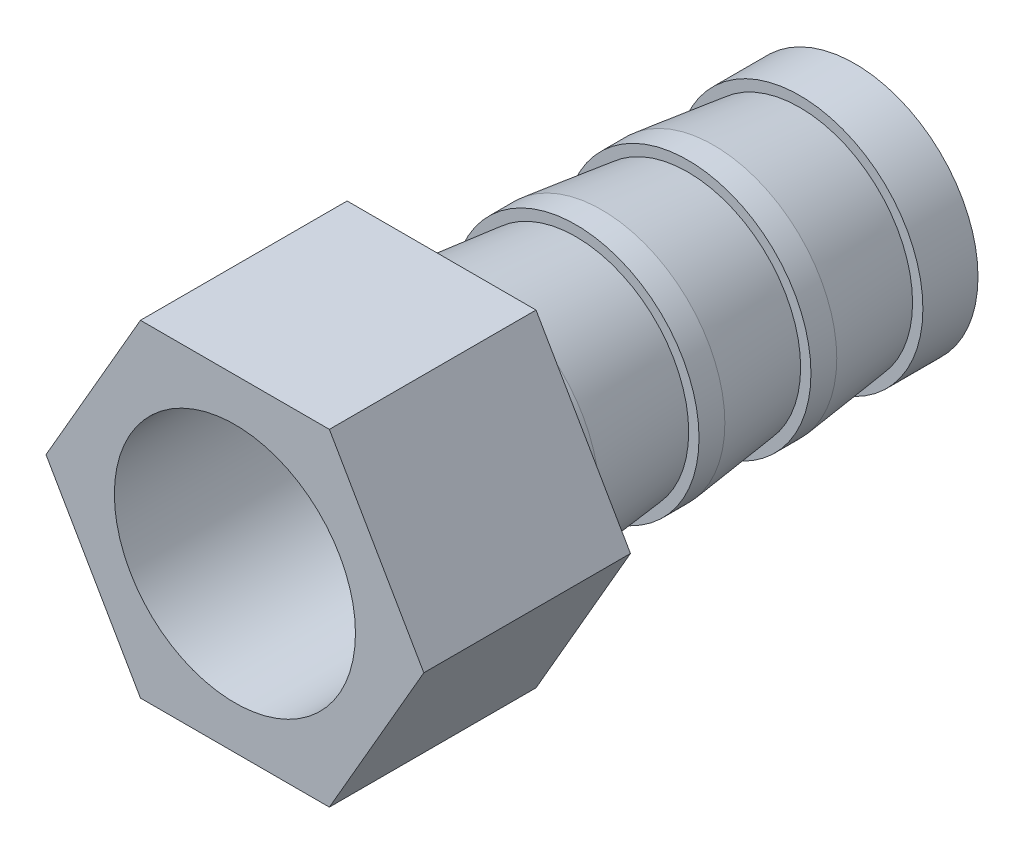
SolidWorks part; units mm, degrees
material "黄铜"
ref_plane "前视基准面" through (0, 0, 0) normal (0, 0, 1) x (1, 0, 0)
ref_plane "上视基准面" through (0, 0, 0) normal (0, 1, 0) x (1, 0, 0)
ref_plane "右视基准面" through (0, 0, 0) normal (1, 0, 0) x (0, 0, -1)
other "质心 (COM)"
sketch "草图1" plane through (0, 0, 0) normal (0, 0, 1) x (1, 0, 0)
  line L1 (5.4848, 9.5) -> (-5.4848, 9.5)
  line L2 (-5.4848, 9.5) -> (-10.9697, 0)
  line L3 (-10.9697, 0) -> (-5.4848, -9.5)
  line L4 (-5.4848, -9.5) -> (5.4848, -9.5)
  line L5 (5.4848, -9.5) -> (10.9697, 0)
  line L6 (10.9697, 0) -> (5.4848, 9.5)
  circle A0 centre (0, 0) radius 9.5 construction
  circle A1 centre (0, 0) radius 7
  dimension "D2" = 14
  dimension "D1" = 19
extrude "凸台-拉伸1" add sketch "草图1" along normal blind 12
cosmetic thread "装饰螺纹线1" parameters "D2"=16.662
sketch "草图2" plane through (0, 0, 0) normal (0, 1, 0) x (1, 0, 0)
  line L0 (0, 0) -> (0, 24) construction
  line L1 (-7.15, 0) -> (-7.15, 2)
  line L2 (5.4848, 0) -> (-5.4848, 0) construction
  line L3 (-7.15, 2) -> (-6.55, 7.8)
  line L4 (-6.55, 7.8) -> (-7.15, 7.8)
  line L5 (-7.15, 7.8) -> (-7.15, 9.3)
  line L6 (-6.55, 14.3) -> (-7.15, 14.3)
  line L7 (-7.15, 14.3) -> (-7.15, 15.8)
  line L8 (-6.55, 20.8) -> (-7.15, 20.8)
  line L9 (-7.15, 20.8) -> (-7.15, 24)
  line L10 (-7.15, 24) -> (-6, 24)
  line L11 (-6, 24) -> (-6, 0)
  line L12 (-7.15, 9.3) -> (-6.55, 14.3)
  line L13 (-7.15, 15.8) -> (-6.55, 20.8)
  line L14 (-7.15, 0) -> (-6, 0)
  dimension "D1" = 24
  dimension "D2" = 3.2
  dimension "D3" = 12
  dimension "D4" = 14.3
  dimension "D5" = 13.1
  dimension "D6" = 1.5
  dimension "D7" = 6.5
  dimension "D8" = 6.5
  dimension "D9" = 2
revolve "旋转1" add sketch "草图2" angle 360 about L0
ref_axis "工件z轴" through (0, 0, -24) along (0, 0, 1)
ref_plane "基准面1" through (0, 0, 6) normal (0, 0, 1) x (1, 0, 0)
ref_point " "
ref_point "A"
ref_point "B"
